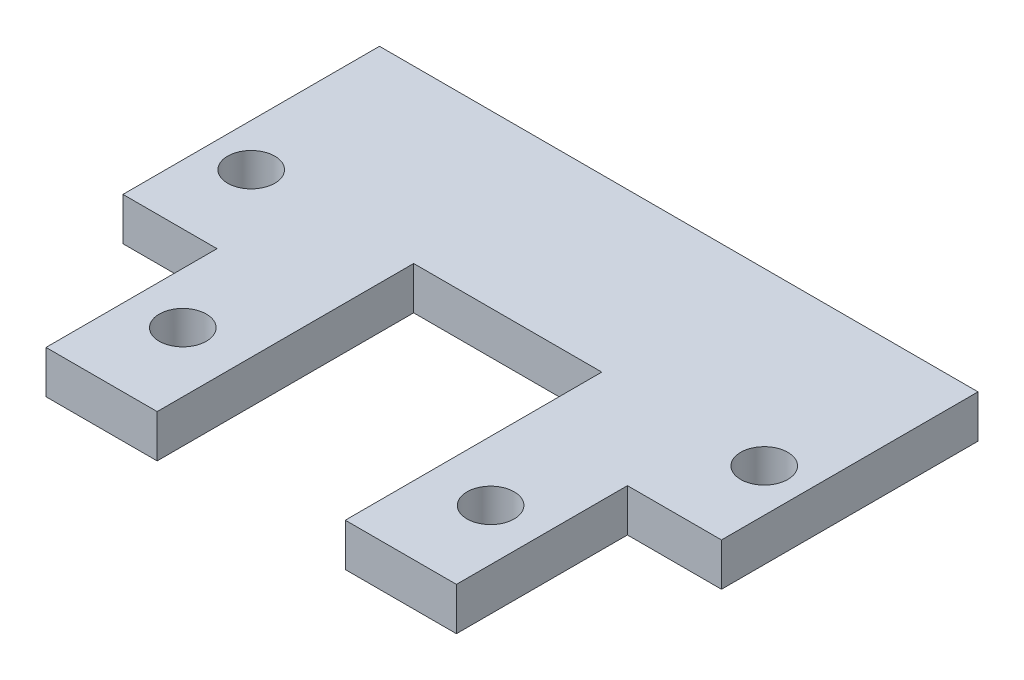
SolidWorks part; units mm, degrees
ref_plane "Front Plane" through (0, 0, 0) normal (1, 0, 0) x (0, 1, 0)
ref_plane "Top Plane" through (0, 0, 0) normal (0, 0, 1) x (0, 1, 0)
ref_plane "Right Plane" through (0, 0, 0) normal (0, 1, 0) x (-1, 0, 0)
sketch "Sketch1" plane through (0, 0, 0) normal (0, 1, 0) x (-1, 0, 0)
  line L1 (19.05, -6.35) -> (-19.05, -6.35) construction
  line L2 (19.05, -6.35) -> (19.05, 6.35) construction
  line L3 (19.05, 6.35) -> (-19.05, 6.35) construction
  line L4 (-19.05, -6.35) -> (-19.05, 6.35) construction
  line L5 (19.05, -6.35) -> (-19.05, 6.35) construction
  line L6 (19.05, 6.35) -> (-19.05, -6.35) construction
  line L7 (7.9375, -6.35) -> (-7.9375, -6.35) construction
  line L8 (7.9375, -6.35) -> (7.9375, 6.35) construction
  line L9 (7.9375, 6.35) -> (-7.9375, 6.35) construction
  line L10 (-7.9375, -6.35) -> (-7.9375, 6.35) construction
  line L11 (7.9375, -6.35) -> (-7.9375, 6.35) construction
  line L12 (7.9375, 6.35) -> (-7.9375, -6.35) construction
  line L13 (22.225, -6.35) -> (-22.225, -6.35)
  line L14 (22.225, -6.35) -> (22.225, 6.35)
  line L15 (22.225, 6.35) -> (-22.225, 6.35)
  line L16 (-22.225, -6.35) -> (-22.225, 6.35)
  line L17 (22.225, -6.35) -> (-22.225, 6.35) construction
  line L18 (22.225, 6.35) -> (-22.225, -6.35) construction
  line L19 (12.7, -3.175) -> (-12.7, -3.175) construction
  line L20 (12.7, -3.175) -> (12.7, 3.175) construction
  line L21 (12.7, 3.175) -> (-12.7, 3.175) construction
  line L22 (-12.7, -3.175) -> (-12.7, 3.175) construction
  line L23 (12.7, -3.175) -> (-12.7, 3.175) construction
  line L24 (12.7, 3.175) -> (-12.7, -3.175) construction
  line L25 (-15.24, 6.35) -> (15.24, 6.35)
  line L26 (-15.24, 6.35) -> (-15.24, 19.05)
  line L27 (-15.24, 19.05) -> (15.24, 19.05)
  line L28 (15.24, 6.35) -> (15.24, 19.05)
  line L33 (-22.225, -6.35) -> (22.225, -6.35)
  line L34 (-22.225, -6.35) -> (-22.225, -12.7)
  line L35 (-22.225, -12.7) -> (22.225, -12.7)
  line L36 (22.225, -6.35) -> (22.225, -12.7)
  circle A1 centre (19.05, 0) radius 1.75
  circle A2 centre (-19.05, 0) radius 1.75
  circle A5 centre (19.05, 0) radius 9.017 construction
  point P0 (0, 0)
  point P8 (0, 0)
  point P15 (0, 0)
  point P20 (0, 0)
  point P35 (0, 19.05)
  point P36 (0, 19.05)
  dimension "D3" = 3.5
  dimension "D8" = 18.034
  dimension "D1" = 38.1
  dimension "D2" = 12.7
  dimension "D4" = 15.875
  dimension "D5" = 25.4
  dimension "D6" = 6.35
  dimension "D7" = 44.45
  dimension "D9" = 30.48
  dimension "D10" = 6.35
  dimension "D11" = 12.7
extrude "Boss-Extrude1" add sketch "Sketch1" along normal blind 3.175 contours L27 L26 L25 | L16 L13 L14 L15 L25 A2 A1 | L27 L15 L28 | L36 L13 L34 L35 region at (0, 0, -9.525) region at (0, 0, 0) region at (0, 0, 12.7)
sketch "Sketch2" plane through (0, 3.175, 0) normal (0, 1, 0) x (-1, 0, 0)
  line L1 (19.05, -19.05) -> (-19.05, -19.05) construction
  line L2 (19.05, -19.05) -> (19.05, 19.05) construction
  line L3 (19.05, 19.05) -> (-19.05, 19.05) construction
  line L4 (-19.05, -19.05) -> (-19.05, 19.05) construction
  line L5 (19.05, -19.05) -> (-19.05, 19.05) construction
  line L6 (19.05, 19.05) -> (-19.05, -19.05) construction
  line L7 (-6.985, 19.05) -> (6.985, 19.05) construction
  line L8 (-6.985, 19.05) -> (-6.985, 6.35) construction
  line L9 (-6.985, 6.35) -> (6.985, 6.35) construction
  line L10 (6.985, 19.05) -> (6.985, 6.35) construction
  line L11 (-15.24, 6.35) -> (-22.225, 6.35) construction
  line L12 (-15.875, 19.05) -> (-15.875, 6.35) construction
  line L13 (-15.875, 6.35) -> (-6.985, 6.35) construction
  line L14 (0, 6.35) -> (0, 0) construction
  circle A0 centre (-11.43, 12.7) radius 1.75
  circle A1 centre (11.43, 12.7) radius 1.75
  point P0 (0, 0)
  point P13 (0, 6.35)
  point P14 (-11.43, 6.35)
  dimension "D5" = 3.5
  dimension "D1" = 38.1
  dimension "D2" = 8.89
  dimension "D3" = 3.175
  dimension "D4" = 6.35
extrude "Cut-Extrude1" cut sketch "Sketch2" against normal blind 12.192
sketch "Sketch3" plane through (0, 3.175, 0) normal (0, 1, 0) x (-1, 0, 0)
  line L0 (-15.24, 19.05) -> (15.24, 19.05) construction
  line L1 (-6.985, 19.05) -> (6.985, 19.05)
  line L2 (-6.985, 19.05) -> (-6.985, 0)
  line L3 (-6.985, 0) -> (6.985, 0)
  line L4 (6.985, 19.05) -> (6.985, 0)
  point P6 (0, 0)
  dimension "D1" = 13.97
  dimension "D2" = 19.05
extrude "Cut-Extrude2" cut sketch "Sketch3" against normal blind 25.4
